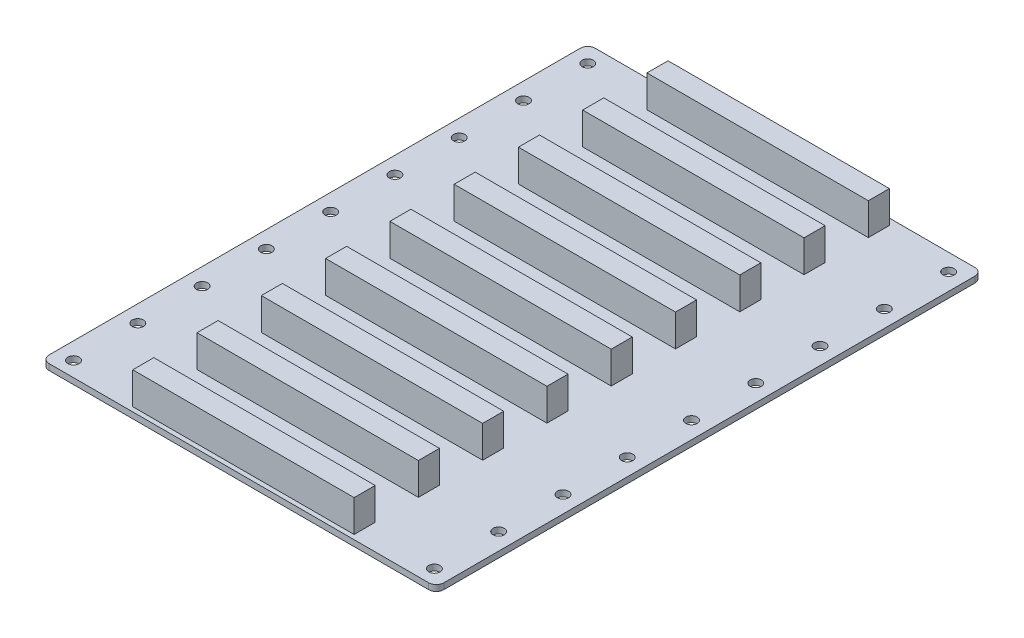
SolidWorks part; units mm, degrees
ref_plane "Front Plane" through (0, 0, 0) normal (0, 0, 1) x (1, 0, 0)
ref_plane "Top Plane" through (0, 0, 0) normal (0, 1, 0) x (1, 0, 0)
ref_plane "Right Plane" through (0, 0, 0) normal (1, 0, 0) x (0, 0, -1)
sketch "Sketch1" plane through (0, 0, 0) normal (0, 1, 0) x (1, 0, 0)
  line L1 (-52.5, -72.65) -> (52.5, -72.65)
  line L2 (-52.5, -72.65) -> (-52.5, 72.65)
  line L3 (-52.5, 72.65) -> (52.5, 72.65)
  line L4 (52.5, -72.65) -> (52.5, 72.65)
  line L5 (-52.5, -72.65) -> (52.5, 72.65) construction
  line L6 (-52.5, 72.65) -> (52.5, -72.65) construction
  point P0 (0, 0)
  dimension "D1" = 105
  dimension "D2" = 145.3
extrude "Boss-Extrude1" add sketch "Sketch1" along normal blind 1.6
sketch "Sketch3" plane through (0, 1.6, 0) normal (0, 1, 0) x (1, 0, 0)
  line L0 (0, 72.65) -> (0, -72.65) construction
  line L1 (52.5, 72.65) -> (-52.5, 72.65) construction
  line L2 (-52.5, -72.65) -> (52.5, -72.65) construction
  line L4 (-52.5, 72.65) -> (-52.5, -72.65) construction
  circle A1 centre (-48, -68.65) radius 1.5
  circle A3 centre (-48, -51.55) radius 1.5
  circle A4 centre (-48, -34.45) radius 1.5
  circle A5 centre (-48, -17.35) radius 1.5
  circle A6 centre (-48, -0.25) radius 1.5
  circle A7 centre (-48, 16.85) radius 1.5
  circle A8 centre (-48, 33.95) radius 1.5
  circle A9 centre (-48, 51.05) radius 1.5
  circle A10 centre (-48, 68.15) radius 1.5
  circle A11 centre (48, 68.15) radius 1.5
  circle A12 centre (48, 51.05) radius 1.5
  circle A13 centre (48, 33.95) radius 1.5
  circle A14 centre (48, 16.85) radius 1.5
  circle A15 centre (48, -0.25) radius 1.5
  circle A16 centre (48, -17.35) radius 1.5
  circle A17 centre (48, -34.45) radius 1.5
  circle A18 centre (48, -51.55) radius 1.5
  circle A19 centre (48, -68.65) radius 1.5
  dimension "D1" = 3
  dimension "D2" = 4.5
  dimension "D3" = 9
  dimension "D4" = 17.1
  dimension "D5" = 4
extrude "Cut-Extrude2" cut sketch "Sketch3" against normal up to surface (1.6 mm away) up to face at (0, 0, 0)
sketch "Sketch4" plane through (0, 1.6, 0) normal (0, 1, 0) x (1, 0, 0)
  line L0 (-29.445, -54.35) -> (-29.445, -48.75)
  line L1 (-29.445, -71.45) -> (29.445, -71.45)
  line L2 (-29.445, -71.45) -> (-29.445, -65.85)
  line L3 (-29.445, -65.85) -> (29.445, -65.85)
  line L4 (29.445, -71.45) -> (29.445, -65.85)
  line L5 (-29.445, -71.45) -> (29.445, -65.85) construction
  line L6 (-29.445, -65.85) -> (29.445, -71.45) construction
  line L7 (-52.5, -72.65) -> (52.5, -72.65) construction
  line L8 (52.5, -72.65) -> (52.5, 72.65) construction
  line L9 (-29.445, -54.35) -> (29.445, -54.35)
  line L10 (29.445, -54.35) -> (29.445, -48.75)
  line L11 (-29.445, -48.75) -> (29.445, -48.75)
  line L12 (-29.445, -37.25) -> (-29.445, -31.65)
  line L13 (-29.445, -37.25) -> (29.445, -37.25)
  line L14 (29.445, -37.25) -> (29.445, -31.65)
  line L15 (-29.445, -31.65) -> (29.445, -31.65)
  line L16 (-29.445, -20.15) -> (-29.445, -14.55)
  line L17 (-29.445, -20.15) -> (29.445, -20.15)
  line L18 (29.445, -20.15) -> (29.445, -14.55)
  line L19 (-29.445, -14.55) -> (29.445, -14.55)
  line L20 (-29.445, -3.05) -> (-29.445, 2.55)
  line L21 (-29.445, -3.05) -> (29.445, -3.05)
  line L22 (29.445, -3.05) -> (29.445, 2.55)
  line L23 (-29.445, 2.55) -> (29.445, 2.55)
  line L24 (-29.445, 14.05) -> (-29.445, 19.65)
  line L25 (-29.445, 14.05) -> (29.445, 14.05)
  line L26 (29.445, 14.05) -> (29.445, 19.65)
  line L27 (-29.445, 19.65) -> (29.445, 19.65)
  line L28 (-29.445, 31.15) -> (-29.445, 36.75)
  line L29 (-29.445, 31.15) -> (29.445, 31.15)
  line L30 (29.445, 31.15) -> (29.445, 36.75)
  line L31 (-29.445, 36.75) -> (29.445, 36.75)
  line L32 (-29.445, 48.25) -> (-29.445, 53.85)
  line L33 (-29.445, 48.25) -> (29.445, 48.25)
  line L34 (29.445, 48.25) -> (29.445, 53.85)
  line L35 (-29.445, 53.85) -> (29.445, 53.85)
  line L36 (-29.445, 65.35) -> (-29.445, 70.95)
  line L37 (-29.445, 65.35) -> (29.445, 65.35)
  line L38 (29.445, 65.35) -> (29.445, 70.95)
  line L39 (-29.445, 70.95) -> (29.445, 70.95)
  point P0 (0, -68.65)
  dimension "D1" = 5.6
  dimension "D2" = 58.89
  dimension "D3" = 4
  dimension "D4" = 52.5
  dimension "D6" = 11.5
  dimension "D5" = 9
extrude "Boss-Extrude2" add sketch "Sketch4" along normal blind 8.5
fillet "Fillet2" radius 2 4 edges at (-52.5, 0.8, -72.65) (52.5, 0.8, -72.65) (52.5, 0.8, 72.65) (-52.5, 0.8, 72.65)
